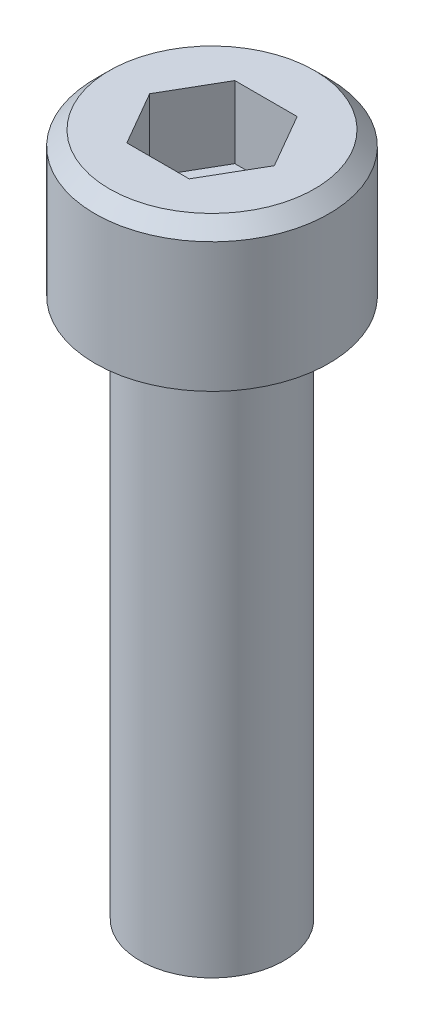
SolidWorks part; units mm, degrees
material "Alloy Steel"
ref_plane "Front (1)" through (0, 0, 0) normal (0, 0, 1) x (1, 0, 0)
ref_plane "Top (2)" through (0, 0, 0) normal (0, 1, 0) x (1, 0, 0)
ref_plane "Right (3)" through (0, 0, 0) normal (1, 0, 0) x (0, 0, -1)
ref_axis "X Axis" through (13.5064, 0, 0) along (-1, 0, 0)
ref_axis "Y Axis" through (0, 12.3593, 0) along (0, -1, 0)
ref_axis "Z Axis" through (0, 0, 14.1119) along (0, 0, -1)
sketch "Sketch1" plane through (0, 0, 0) normal (0, 0, 1) x (1, 0, 0)
  line L0 (0, 0) -> (0, 11.5732) construction
  line L1 (0, 8) -> (6.5, 8)
  line L2 (0, 8) -> (0, -30)
  line L3 (0, -30) -> (4, -30)
  line L4 (6.5, 8) -> (6.5, 0)
  line L7 (6.5, 0) -> (4, 0)
  line L8 (4, -30) -> (4, 0)
  dimension "Major" = 8
  dimension "Length" = 30
  dimension "Head Diameter" = 13
  dimension "Head Height" = 8
revolve "Revolve1" add sketch "Sketch1" angle 360 about L0
cosmetic thread "Cosmetic Thread1" parameters "D1"=28, "D2"=6.619
sketch "Sketch2" plane through (0, 8, 0) normal (0, 1, 0) x (1, 0, 0)
  line L1 (3.4641, 0) -> (1.7321, 3)
  line L2 (1.7321, 3) -> (-1.7321, 3)
  line L3 (-1.7321, 3) -> (-3.4641, 0)
  line L4 (-3.4641, 0) -> (-1.7321, -3)
  line L5 (-1.7321, -3) -> (1.7321, -3)
  line L6 (1.7321, -3) -> (3.4641, 0)
  circle A0 centre (0, 0) radius 3 construction
  dimension "Key Size" = 6
extrude "Cut-Extrude1" cut sketch "Sketch2" against normal blind 4
chamfer "Chamfer1" distance 0.8 angle 45 1 edges at (0, 8, -6.5)
